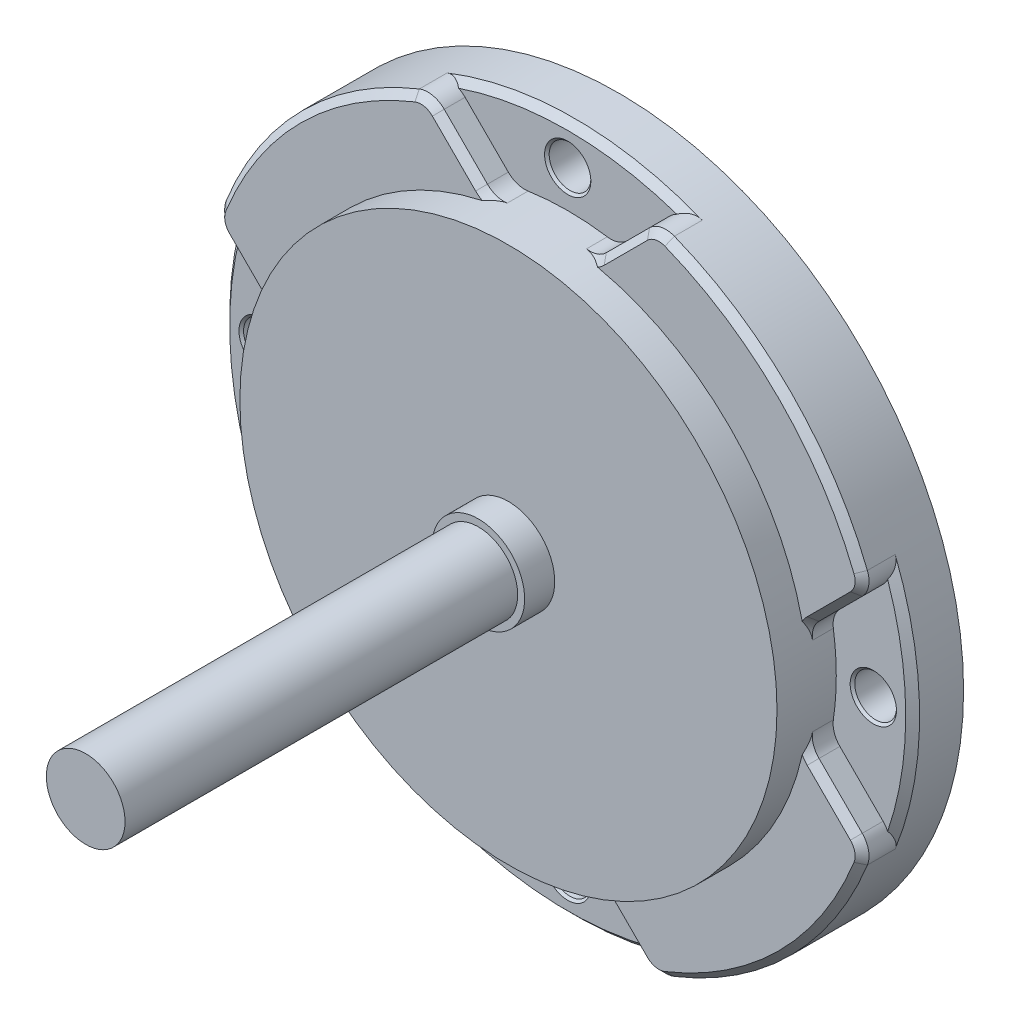
SolidWorks part; units mm, degrees
ref_plane "Front Plane" through (0, 0, 0) normal (0, 0, 1) x (1, 0, 0)
ref_plane "Top Plane" through (0, 0, 0) normal (0, 1, 0) x (1, 0, 0)
ref_plane "Right Plane" through (0, 0, 0) normal (1, 0, 0) x (0, 0, -1)
sketch "Sketch1" plane through (0, 0, 0) normal (0, 0, 1) x (1, 0, 0)
  circle A0 centre (0, 0) radius 74.5
  dimension "D1" = 149
extrude "Boss-Extrude1" add sketch "Sketch1" along normal blind 17
sketch "Sketch2" plane through (0, 0, 17) normal (0, 0, 1) x (1, 0, 0)
  circle A0 centre (0, 0) radius 66 construction
  circle A1 centre (0, 0) radius 74.5 construction
  circle A2 centre (0, 66) radius 4.5
  circle A3 centre (66, 0) radius 4.5
  circle A4 centre (0, -66) radius 4.5
  circle A5 centre (-66, 0) radius 4.5
  point P7 (34.5177, -9.4365)
  point P8 (0, 0)
  point P16 (0, 0)
  dimension "D1" = 8.5
  dimension "D2" = 9
  dimension "D3" = 4
extrude "Cut-Extrude1" cut sketch "Sketch2" against normal blind 17
sketch "Sketch3" plane through (0, 0, 17) normal (0, 0, 1) x (1, 0, 0)
  line L1 (11, -56.9473) -> (24.4324, -70.3797)
  line L2 (-11, -56.9473) -> (-11, -73.6834) construction
  line L3 (-56.9473, 11) -> (-70.3797, 24.4324)
  line L5 (11, 56.9473) -> (24.4324, 70.3797)
  line L6 (-11, 56.9473) -> (-24.4324, 70.3797)
  line L7 (56.9473, -11) -> (70.3797, -24.4324)
  line L8 (56.9473, 11) -> (70.3797, 24.4324)
  line L9 (-56.9473, -11) -> (-70.3797, -24.4324) [skipped]
  arc A0 (-11, -56.9473) -> (11, -56.9473) centre (0, 0) ccw
  circle A1 centre (0, 0) radius 74.5 construction
  arc A2 (-24.4324, -70.3797) -> (24.4324, -70.3797) centre (0, 0) ccw
  arc A3 (70.3797, -24.4324) -> (70.3797, 24.4324) centre (0, 0) ccw
  arc A4 (56.9473, -11) -> (56.9473, 11) centre (0, 0) ccw
  arc A5 (24.4324, 70.3797) -> (-24.4324, 70.3797) centre (0, 0) ccw
  arc A6 (11, 56.9473) -> (-11, 56.9473) centre (0, 0) ccw
  arc A7 (-70.3797, 24.4324) -> (-24.4324, -70.3797) centre (0, 0) ccw
  arc A8 (-56.9473, 11) -> (-11, -56.9473) centre (0, 0) ccw
  point P9 (0, 0)
  point P12 (-56.9473, -11)
  point P25 (0, 0)
  dimension "D1" = 116
  dimension "D3" = 22
  dimension "D4" = 4
extrude "Cut-Extrude2" cut sketch "Sketch3" against normal blind 6
sketch "Sketch4" plane through (0, 0, 17) normal (0, 0, 1) x (1, 0, 0)
  circle A1 centre (0, 0) radius 58
  arc A2 (-56.9473, 11) -> (11, -56.9473) centre (0, 0) ccw construction
extrude "Boss-Extrude2" add sketch "Sketch4" along normal blind 6.8
fillet "Fillet1" radius 5 12 edges at (24.4324, -70.3797, 14) (-70.3797, 24.4324, 14) (-24.4324, 70.3797, 14) (24.4324, 70.3797, 14) (70.3797, 24.4324, 14) (70.3797, -24.4324, 14) (56.9473, -11, 14) (11, -56.9473, 14) (-56.9473, 11, 14) (-11, 56.9473, 14) (11, 56.9473, 14) (56.9473, 11, 14)
chamfer "Chamfer1" distance 1.5 angle 45 24 edges at (-52.6795, -52.6795, 11) (74.5, 0, 11) (0, 74.5, 11) (57.5627, -10.8591, 17) (63.4427, -17.4953, 17) (69.4714, -24.6885, 17) (52.6795, -52.6795, 17) (24.6885, -69.4714, 17) (17.4953, -63.4427, 17) (10.8591, -57.5627, 17) (-57.5627, 10.8591, 17) (-63.4427, 17.4953, 17) (-69.4714, 24.6885, 17) (-52.6795, 52.6795, 17) (-24.6885, 69.4714, 17) (-17.4953, 63.4427, 17) (-10.8591, 57.5627, 17) (10.8591, 57.5627, 17) (17.4953, 63.4427, 17) (24.6885, 69.4714, 17) (52.6795, 52.6795, 17) (69.4714, 24.6885, 17) (63.4427, 17.4953, 17) (57.5627, 10.8591, 17)
chamfer "Chamfer2" distance 0.5 angle 45 4 edges at (70.5, 0, 11) (4.5, -66, 11) (-61.5, 0, 11) (4.5, 66, 11)
sketch "Sketch5" plane through (0, 0, 23.8) normal (0, 0, 1) x (1, 0, 0)
  circle A0 centre (0, 0) radius 8.5
  dimension "D1" = 17
extrude "Boss-Extrude3" add sketch "Sketch5" along normal blind 91.3
sketch "Sketch6" plane through (0, 0, 23.8) normal (0, 0, 1) x (1, 0, 0)
  circle A0 centre (0, 0) radius 10
  dimension "D1" = 20
extrude "Boss-Extrude4" add sketch "Sketch6" along normal blind 6.5
